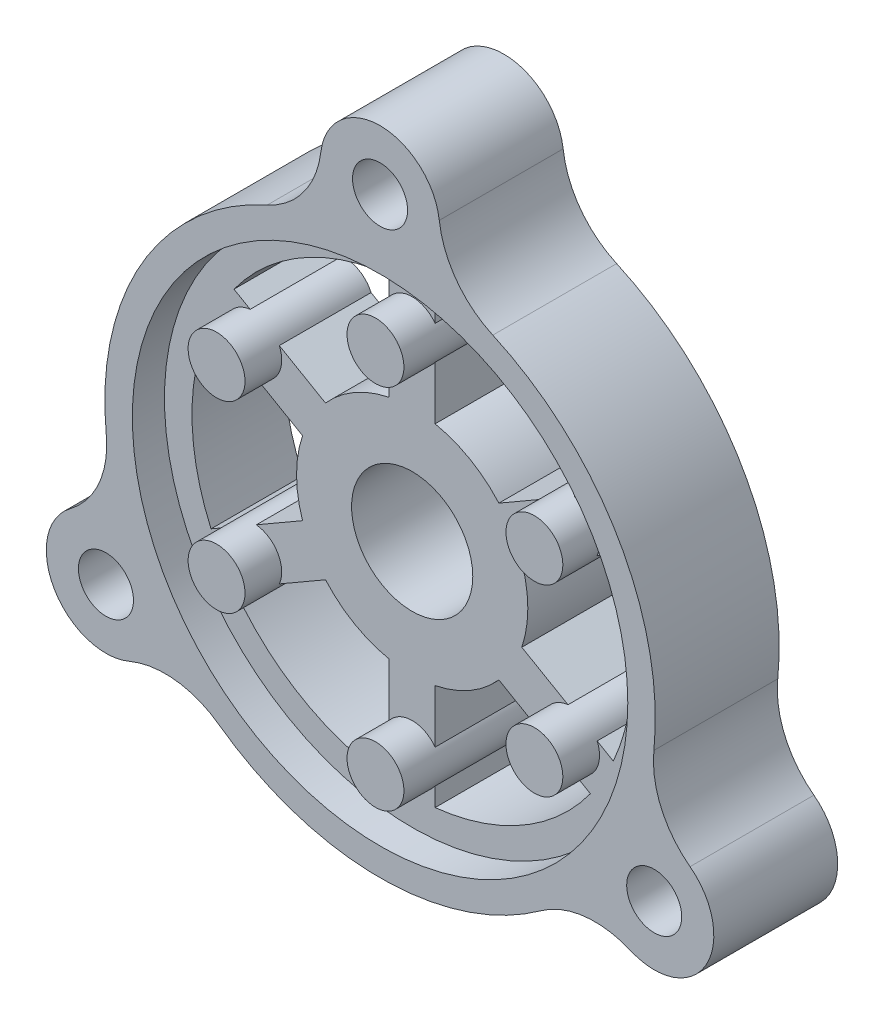
SolidWorks part; units mm, degrees
note: '?' marks a value the reader was unsure of.
ref_plane "Front Plane" through (0, 0, 0) normal (0, 0, 1) x (1, 0, 0)
ref_plane "Top Plane" through (0, 0, 0) normal (0, 1, 0) x (1, 0, 0)
ref_plane "Right Plane" through (0, 0, 0) normal (1, 0, 0) x (0, 0, -1)
sketch "Sketch1" plane through (0, 0, 0) normal (0, 0, 1) x (1, 0, 0)
  circle A0 centre (0, 0) radius 15
  dimension "D1" = 30
extrude "Boss-Extrude1" add sketch "Sketch1" along normal blind 5
sketch "Sketch2" plane through (0, 0, 5) normal (0, 0, 1) x (1, 0, 0)
  circle A0 centre (0, 0) radius 12
  circle A1 centre (0, 0) radius 6.302
  circle A2 centre (0, 0) radius 3.302
  circle A3 centre (0, 0) radius 15 construction
  dimension "D1" = 6.604
  dimension "D2" = 3
  dimension "D3" = 3
extrude "Cut-Extrude1" cut sketch "Sketch2" against normal through all contours A2 | A0 A1
sketch "Sketch4" plane through (0, 0, 0) normal (0, 0, 1) x (1, 0, 0)
  line L1 (0, 10) -> (-8.6603, 5) construction
  line L2 (-8.6603, 5) -> (-8.6603, -5) construction
  line L3 (-8.6603, -5) -> (0, -10) construction
  line L4 (0, -10) -> (8.6603, -5) construction
  line L5 (8.6603, -5) -> (8.6603, 5) construction
  line L6 (8.6603, 5) -> (0, 10) construction
  circle A0 centre (0, 0) radius 8.6603 construction
  circle A1 centre (0, 10) radius 1.55
  circle A2 centre (-8.6603, 5) radius 1.55
  circle A3 centre (-8.6603, -5) radius 1.55
  circle A4 centre (0, -10) radius 1.55
  circle A5 centre (8.6603, -5) radius 1.55
  circle A6 centre (8.6603, 5) radius 1.55
  dimension "D2" = 3.1
  dimension "D1" = 20
extrude "Boss-Extrude2" add sketch "Sketch4" along normal offset from surface (7 mm away) 2 up to face at (12, 0, 5) offset beyond the face yes
sketch "Sketch5" plane through (0, 0, 0) normal (0, 0, -1) x (-1, 0, 0)
  line L1 (1.25, 14.9478) -> (-1.25, 14.9478)
  line L2 (1.25, 14.9478) -> (1.25, 6.1768)
  line L3 (1.25, 6.1768) -> (-1.25, 6.1768)
  line L4 (-1.25, 14.9478) -> (-1.25, 6.1768)
  circle A0 centre (0, 0) radius 15 construction
  circle A1 centre (0, 0) radius 6.302 construction
  dimension "D1" = 2.5
extrude "Boss-Extrude3" add sketch "Sketch5" against normal up to surface (5 mm away)
ref_axis "Axis1" through (0, 0, 0) along (0, 0, 1)?
pattern_circular "CirPattern1" count 6 every 60 about axis through (0, 0, 0) along (0, 0, 1) of "Boss-Extrude3"
sketch "Sketch6" plane through (0, 0, 5) normal (0, 0, 1) x (1, 0, 0)
  circle A0 centre (0, 0) radius 15
  circle A1 centre (0, 0) radius 13.5
  circle A2 centre (0, 0) radius 15 construction
  dimension "D1" = 27
extrude "Boss-Extrude4" add sketch "Sketch6" along normal blind 1.75
sketch "Sketch7" plane through (0, 0, 0) normal (0, 0, -1) x (-1, 0, 0)
  line L0 (0, 17.25) -> (0, 0) construction
  circle A0 centre (0, 17.25) radius 3.25
  circle A1 centre (0, 17.25) radius 1.5
  dimension "D1" = 3
  dimension "D2" = 6.5
  dimension "D3" = 17.25
extrude "Boss-Extrude5" add sketch "Sketch7" against normal up to surface (6.75 mm away) up to face at (15, 0, 6.75)
fillet "Fillet2" radius 5 2 edges at (2.1811, 14.8406, 3.375) (-2.1811, 14.8406, 3.375)
pattern_circular "CirPattern2" count 3 every 120 about axis through (0, 0, 0) along (0, 0, 1) of "Fillet2", "Boss-Extrude5"
